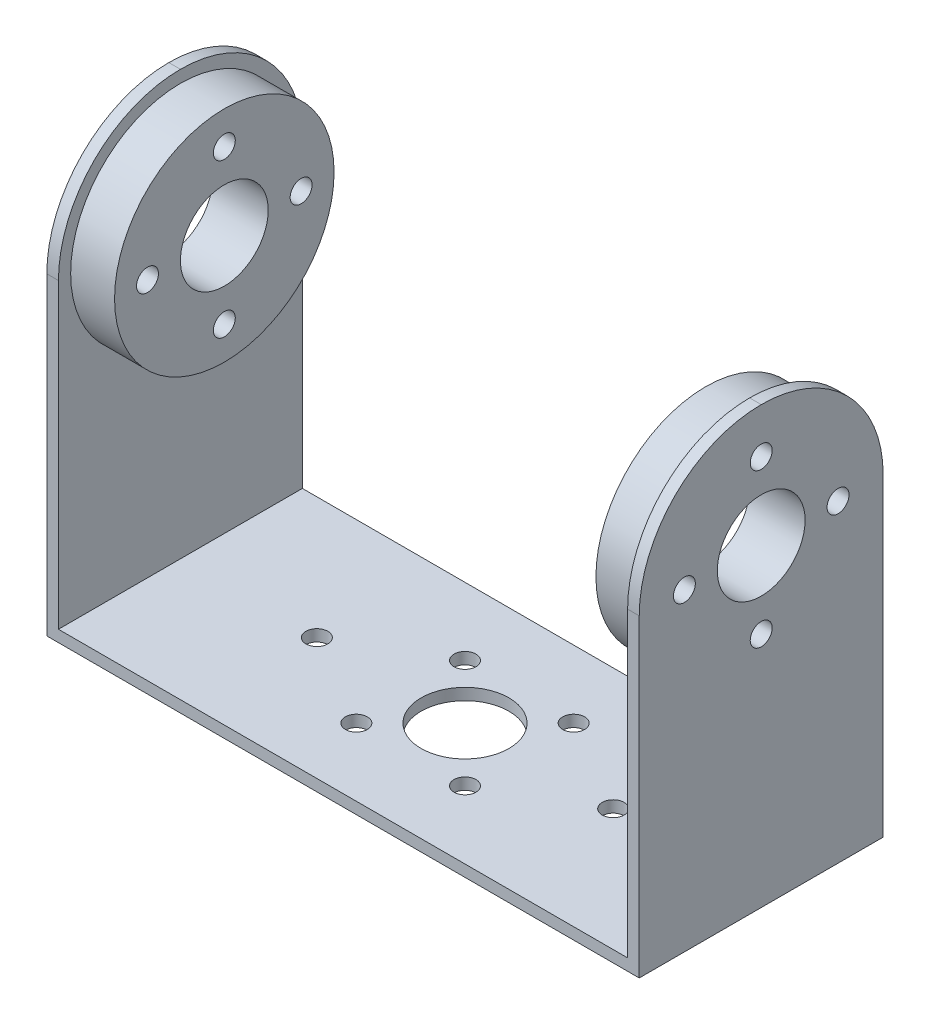
SolidWorks part; units mm, degrees
ref_plane "Front Plane" through (0, 0, 0) normal (0, 0, 1) x (1, 0, 0)
ref_plane "Top Plane" through (0, 0, 0) normal (0, 1, 0) x (1, 0, 0)
ref_plane "Right Plane" through (0, 0, 0) normal (1, 0, 0) x (0, 0, -1)
sketch "Sketch2" plane through (0, 0, 0) normal (0, 0, 1) x (1, 0, 0)
  line L0 (0, 39.6875) -> (0, 0)
  line L1 (0, -55) -> (0, 55) construction
  line L2 (0, 0) -> (53.975, 0)
  line L3 (55, 0) -> (-55, 0) construction
  line L4 (53.975, 0) -> (53.975, 39.6875)
  line L5 (53.975, 39.6875) -> (52.9167, 39.6875)
  line L6 (52.9167, 39.6875) -> (52.9167, 1.0583)
  line L7 (52.9167, 1.0583) -> (1.0583, 1.0583)
  line L8 (1.0583, 1.0583) -> (1.0583, 39.6875)
  line L9 (1.0583, 39.6875) -> (0, 39.6875)
  dimension "D1" = 53.975
  dimension "D2" = 39.6875
  dimension "D3" = 1.0583
  dimension "D4" = 1.0583
extrude "Boss-Extrude1" add sketch "Sketch2" along normal blind 22.225
fillet "Fillet1" radius 11.1125 4 edges at (0.5292, 39.6875, 0) (0.5292, 39.6875, 22.225) (53.4458, 39.6875, 0) (53.4458, 39.6875, 22.225)
sketch "Sketch4" plane through (53.975, 0, 0) normal (1, 0, 0) x (0, 0, -1)
  circle A0 centre (-11.1125, 28.575) radius 4
  circle A1 centre (-11.1125, 35.575) radius 1
  dimension "D1" = 8
  dimension "D3" = 2
  dimension "D2" = 7
extrude "Cut-Extrude1" cut sketch "Sketch4" against normal up to surface (53.975 mm away) up to face at (0, 20.2881, 11.1125)
pattern_circular "CirPattern1" count 4 over 360 about axis through (-11.3137, 28.575, 11.1125) along (1, 0, 0) of "Cut-Extrude1"
sketch "Sketch5" plane through (0, 0, 0) normal (0, -1, 0) x (1, 0, 0)
  line L0 (0, 0) -> (53.975, 0) construction
  line L1 (0, 22.225) -> (53.975, 22.225) construction
  line L2 (0, 0) -> (53.975, 0) construction
  line L3 (0, 22.225) -> (53.975, 22.225) construction
  line L4 (53.975, 22.225) -> (0, 0) construction
  line L5 (38.1, 22.225) -> (15.875, 0) construction
  circle A0 centre (26.9875, 11.1125) radius 4
  circle A1 centre (22.0378, 6.1628) radius 1
  point P8 (26.9875, 11.1125)
  dimension "D1" = 8
  dimension "D3" = 2
  dimension "D2" = 45
  dimension "D4" = 7
extrude "Cut-Extrude2" cut sketch "Sketch5" against normal up to surface (1.0583 mm away) up to face at (26.9875, 1.0583, 11.1125)
pattern_circular "CirPattern2" count 4 over 360 about axis through (26.9875, 12.372, 11.1125) along (0, -1, 0) of "Cut-Extrude2"
sketch "Sketch6" plane through (0, 0, 0) normal (0, -1, 0) x (1, 0, 0)
  line L0 (13.4875, 11.1125) -> (40.4875, 11.1125) construction
  circle A0 centre (26.9875, 11.1125) radius 4 construction
  circle A1 centre (26.9875, 11.1125) radius 4 construction
  circle A2 centre (13.4875, 11.1125) radius 1
  circle A3 centre (40.4875, 11.1125) radius 1
  point P5 (26.9875, 11.1125)
  dimension "D2" = 2
  dimension "D1" = 27
extrude "Cut-Extrude3" cut sketch "Sketch6" against normal up to surface (1.0583 mm away) up to face at (32.9372, 1.0583, 16.0622)
sketch "Sketch7" plane through (1.0583, 0, 0) normal (1, 0, 0) x (0, 0, -1)
  circle A0 centre (-11.1125, 28.575) radius 10
  circle A1 centre (-18.1125, 28.575) radius 1 construction
  circle A2 centre (-11.1125, 21.575) radius 1 construction
  circle A3 centre (-4.1125, 28.575) radius 1 construction
  circle A4 centre (-11.1125, 35.575) radius 1 construction
  circle A5 centre (-11.1125, 28.575) radius 4 construction
  circle A6 centre (-18.1125, 28.575) radius 1
  circle A7 centre (-11.1125, 21.575) radius 1
  circle A8 centre (-4.1125, 28.575) radius 1
  circle A9 centre (-11.1125, 35.575) radius 1
  circle A10 centre (-11.1125, 28.575) radius 4
  dimension "D1" = 20
extrude "Boss-Extrude2" add sketch "Sketch7" along normal blind 4
ref_plane "Plane1" through (26.9875, 0, 0) normal (-1, 0, 0) x (0, 0, 1)
mirror "Mirror1" about plane through (26.9875, 0, 0) normal (-1, 0, 0) of "Boss-Extrude2"
